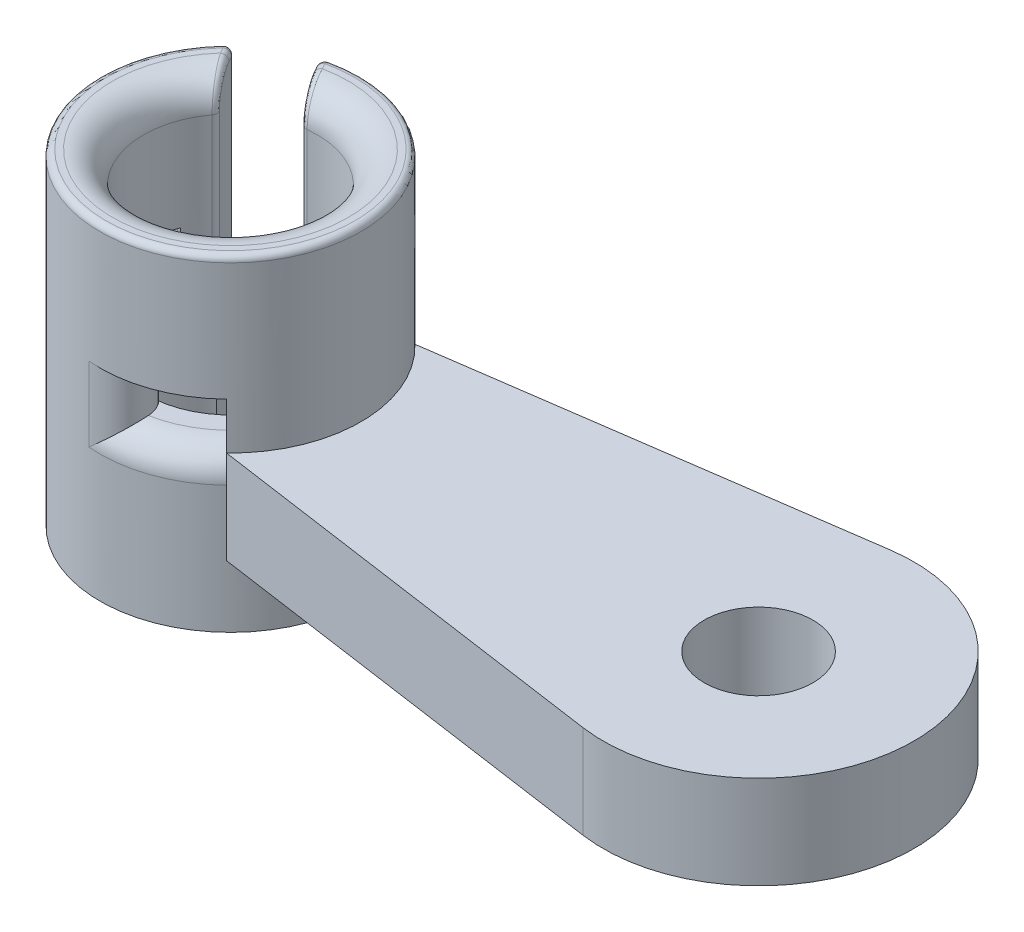
SolidWorks part; units mm, degrees
ref_plane "Front Plane" through (0, 0, 0) normal (0, 0, 1) x (1, 0, 0)
ref_plane "Top Plane" through (0, 0, 0) normal (0, 1, 0) x (1, 0, 0)
ref_plane "Right Plane" through (0, 0, 0) normal (1, 0, 0) x (0, 0, -1)
sketch "Sketch1" plane through (0, 0, 0) normal (0, 1, 0) x (1, 0, 0)
  circle A0 centre (0, 0) radius 2.7
  circle A1 centre (0, 0) radius 4.2
  dimension "D1" = 5.4
  dimension "D2" = 1.5
extrude "Boss-Extrude1" add sketch "Sketch1" along normal blind 5
sketch "Sketch2" plane through (0, 5, 0) normal (0, 1, 0) x (1, 0, 0)
  line L0 (-4.0792, 1) -> (-2.6153, 1)
  line L1 (-4.0792, -1) -> (-2.6153, -1)
  line L2 (0, 0) -> (-4.4135, 0) construction
  line L3 (2.9056, 3.0327) -> (2.1737, 1.765)
  line L4 (1.1736, 4.0327) -> (0.4416, 2.765)
  line L5 (1.1736, -4.0327) -> (0.4416, -2.765)
  line L6 (2.9056, -3.0327) -> (2.1737, -1.765)
  arc A0 (0.4416, 2.765) -> (-2.6153, 1) centre (0, 0) ccw
  arc A1 (1.1736, 4.0327) -> (-4.0792, 1) centre (0, 0) ccw
  circle A2 centre (0, 0) radius 4.2 construction
  circle A3 centre (0, 0) radius 2.8
  arc A4 (-2.6153, -1) -> (0.4416, -2.765) centre (0, 0) ccw
  arc A5 (-4.0792, -1) -> (1.1736, -4.0327) centre (0, 0) ccw
  arc A6 (2.9056, -3.0327) -> (2.9056, 3.0327) centre (0, 0) ccw
  arc A7 (2.1737, -1.765) -> (2.1737, 1.765) centre (0, 0) ccw
  point P2 (1.1736, -4.0327)
  point P13 (0, 0)
  point P22 (0, 0)
  dimension "D2" = 1
  dimension "D3" = 1
  dimension "D1" = 0.1
  dimension "D4" = 3
extrude "Boss-Extrude2" add sketch "Sketch2" along normal blind 1.5
sketch "Sketch3" plane through (0, 6.5, 0) normal (0, 1, 0) x (1, 0, 0)
  circle A0 centre (0, 0) radius 2.8
  circle A1 centre (0, 0) radius 4.2
extrude "Boss-Extrude3" add sketch "Sketch3" along normal blind 4
sketch "Sketch4" plane through (0, 10.5, 0) normal (0, 1, 0) x (1, 0, 0)
  line L0 (-2.9056, 3.0327) -> (-2.12, 1.672)
  line L1 (-1.1736, 4.0327) -> (-0.388, 2.672)
  line L2 (0, 0) -> (-2.1, 3.6373) construction
  line L9 (2.1737, 1.765) -> (2.9056, 3.0327)
  line L10 (1.1736, 4.0327) -> (0.4416, 2.765)
  line L11 (-2.6153, 1) -> (-4.0792, 1)
  line L12 (-4.0792, -1) -> (-2.6153, -1)
  line L13 (0.4416, -2.765) -> (1.1736, -4.0327)
  line L14 (2.9056, -3.0327) -> (2.1737, -1.765)
  line L15 (2.1737, 1.765) -> (2.9056, 3.0327)
  line L16 (1.1736, 4.0327) -> (0.4416, 2.765)
  line L17 (-2.6153, 1) -> (-4.0792, 1)
  line L18 (-4.0792, -1) -> (-2.6153, -1)
  line L19 (0.4416, -2.765) -> (1.1736, -4.0327)
  line L20 (2.9056, -3.0327) -> (2.1737, -1.765)
  circle A0 centre (0, 0) radius 4.2 construction
  circle A1 centre (0, 0) radius 2.7 construction
  circle A2 centre (0, 0) radius 2.7
  circle A3 centre (0, 0) radius 4.2
  circle A4 centre (0, 0) radius 4.2
  arc A8 (2.1737, -1.765) -> (2.1737, 1.765) centre (0, 0) ccw
  arc A9 (2.9056, 3.0327) -> (1.1736, 4.0327) centre (0, 0) ccw
  arc A10 (0.4416, 2.765) -> (-2.6153, 1) centre (0, 0) ccw
  arc A11 (-4.0792, 1) -> (-4.0792, -1) centre (0, 0) ccw
  arc A12 (-2.6153, -1) -> (0.4416, -2.765) centre (0, 0) ccw
  arc A13 (1.1736, -4.0327) -> (2.9056, -3.0327) centre (0, 0) ccw
  arc A14 (2.1737, -1.765) -> (2.1737, 1.765) centre (0, 0) ccw
  arc A15 (2.9056, 3.0327) -> (1.1736, 4.0327) centre (0, 0) ccw
  arc A16 (0.4416, 2.765) -> (-2.6153, 1) centre (0, 0) ccw
  arc A17 (-4.0792, 1) -> (-4.0792, -1) centre (0, 0) ccw
  arc A18 (-2.6153, -1) -> (0.4416, -2.765) centre (0, 0) ccw
  arc A19 (1.1736, -4.0327) -> (2.9056, -3.0327) centre (0, 0) ccw
  point P16 (-1.5534, 0.6906)
  circle M18 centre (0, 0) radius 4.2
  circle M19 centre (0, 0) radius 2.8
  dimension "D2" = 1
  dimension "D3" = 1
  dimension "D1" = 0
  dimension "D4" = 0
extrude "Cut-Extrude1" cut sketch "Sketch4" against normal through all contours L2 A4 L0 M19 | A2 L2 L0 M19 | L2 A2 L1 A16 | L2 A16 L1 M18 region at (-2.1607, 10.5, -2.7351) region at (-1.7815, 10.5, -2.074) region at (-1.2883, 10.5, -3.2388) region at (-0.9054, 10.5, -2.5799)
sketch "Sketch5" plane through (0, 5, 0) normal (0, 1, 0) x (1, 0, 0)
  line L0 (0, 0) -> (17, 0) construction
  line L1 (2.9056, 3.0327) -> (16.2912, 4.9495)
  line L2 (2.9056, -3.0327) -> (16.2912, -4.9495)
  line L9 (-2.12, 1.672) -> (-2.1737, 1.765)
  line L10 (-2.6153, 1) -> (-4.0792, 1)
  line L11 (-4.0792, -1) -> (-2.6153, -1)
  line L12 (0.4416, -2.765) -> (1.1736, -4.0327)
  line L13 (2.9056, -3.0327) -> (2.1737, -1.765)
  line L14 (2.1737, 1.765) -> (2.9056, 3.0327)
  line L15 (1.1736, 4.0327) -> (0.4416, 2.765)
  line L16 (-0.4416, 2.765) -> (-0.388, 2.672)
  line L17 (-2.12, 1.672) -> (-2.1737, 1.765)
  line L18 (-2.6153, 1) -> (-4.0792, 1)
  line L19 (-4.0792, -1) -> (-2.6153, -1)
  line L20 (0.4416, -2.765) -> (1.1736, -4.0327)
  line L21 (2.9056, -3.0327) -> (2.1737, -1.765)
  line L22 (2.1737, 1.765) -> (2.9056, 3.0327)
  line L23 (1.1736, 4.0327) -> (0.4416, 2.765)
  line L24 (-0.4416, 2.765) -> (-0.388, 2.672)
  circle A0 centre (17, 0) radius 1.75
  arc A1 (16.2912, -4.9495) -> (16.2912, 4.9495) centre (17, 0) ccw
  arc A2 (-2.9056, 3.0327) -> (-1.1736, 4.0327) centre (0, 0) ccw construction
  arc A3 (-2.9056, 3.0327) -> (-1.1736, 4.0327) centre (0, 0) ccw
  arc A10 (-2.1737, 1.765) -> (-2.6153, 1) centre (0, 0) ccw
  arc A11 (-4.0792, 1) -> (-4.0792, -1) centre (0, 0) ccw
  arc A12 (-2.6153, -1) -> (0.4416, -2.765) centre (0, 0) ccw
  arc A13 (1.1736, -4.0327) -> (2.9056, -3.0327) centre (0, 0) ccw
  arc A14 (2.1737, -1.765) -> (2.1737, 1.765) centre (0, 0) ccw
  arc A15 (2.9056, 3.0327) -> (1.1736, 4.0327) centre (0, 0) ccw
  arc A16 (0.4416, 2.765) -> (-0.4416, 2.765) centre (0, 0) ccw
  arc A17 (-2.12, 1.672) -> (-0.388, 2.672) centre (0, 0) ccw
  arc A18 (-2.1737, 1.765) -> (-2.6153, 1) centre (0, 0) ccw
  arc A19 (-4.0792, 1) -> (-4.0792, -1) centre (0, 0) ccw
  arc A20 (-2.6153, -1) -> (0.4416, -2.765) centre (0, 0) ccw
  arc A21 (1.1736, -4.0327) -> (2.9056, -3.0327) centre (0, 0) ccw
  arc A22 (2.1737, -1.765) -> (2.1737, 1.765) centre (0, 0) ccw
  arc A23 (2.9056, 3.0327) -> (1.1736, 4.0327) centre (0, 0) ccw
  arc A24 (0.4416, 2.765) -> (-0.4416, 2.765) centre (0, 0) ccw
  arc A25 (-2.12, 1.672) -> (-0.388, 2.672) centre (0, 0) ccw
  dimension "D2" = 3.5
  dimension "D3" = 10
  dimension "D1" = 17
  dimension "D4" = 0
extrude "Boss-Extrude4" add sketch "Sketch5" against normal blind 3 contours A3 L2 A1 L1 A0 region at (12.807, 5, 0)
fillet "Fillet1" radius 0.2 2 edges at (-2.9056, 5.25, -3.0327) (-1.1736, 5.25, -4.0327)
fillet "Fillet2" radius 0.9 7 edges at (1.1736, 5.75, 4.0327) (2.1, 5, 3.6373) (-4.0792, 5.75, -1) (-4.0792, 5.75, 1) (-4.2, 5, 0) (1.1736, 5.75, -4.0327) (2.1, 5, -3.6373)
fillet "Fillet3" radius 1 2 edges at (1.35, 0, 2.3383) (1.4, 10.5, 2.4249)
fillet "Fillet4" radius 0.2 9 edges at (-0.4416, 7.25, -2.765) (-0.5468, 10.0966, -2.9472) (-1.0044, 10.5, -3.7397) (-1.0517, 10.5, -3.985) (2.1, 10.5, 3.6373) (-2.9253, 10.5, -2.9033) (-2.7365, 10.5, -2.7397) (-2.1737, 7.25, -1.765) (-2.3613, 10.2628, -2.0899)
